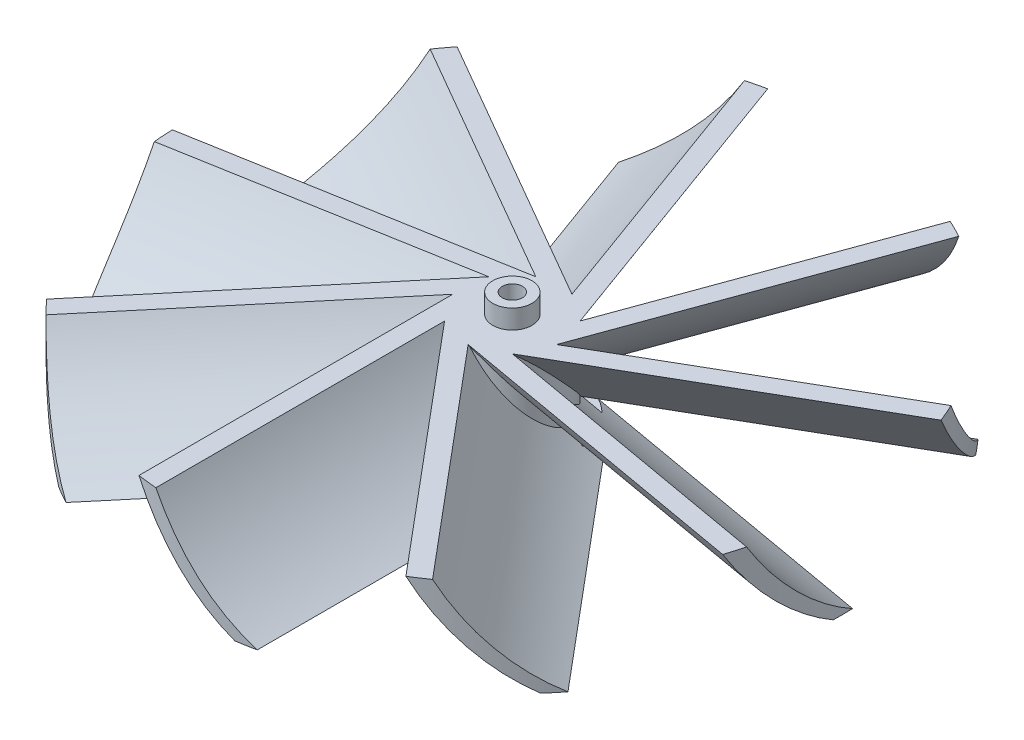
SolidWorks part; units mm, degrees
ref_plane "Front Plane" through (0, 0, 0) normal (0, 0, 1) x (1, 0, 0)
ref_plane "Top Plane" through (0, 0, 0) normal (0, 1, 0) x (1, 0, 0)
ref_plane "Right Plane" through (0, 0, 0) normal (1, 0, 0) x (0, 0, -1)
sketch "Sketch1" plane through (0, 0, 0) normal (0, 1, 0) x (1, 0, 0)
  circle A0 centre (0, 0) radius 5
  dimension "D1" = 10
extrude "Boss-Extrude1" add sketch "Sketch1" along normal blind 5 and the other way blind 5
sketch "Sketch2" plane through (0, 0, 0) normal (0, 0, 1) x (1, 0, 0)
  line L0 (5, 5) -> (-5, 5) construction
  line L1 (-5, 0.8212) -> (5.0825, -5) construction
  line L2 (-4.9175, 5) -> (0.856, -5) construction
  line L3 (-5, 5) -> (5, 5) construction
  line L4 (-5, -5) -> (-5, 5) construction
  line L5 (-5, -5) -> (5, -5) construction
  line L6 (5, 5) -> (5, -5) construction
  line L7 (-5, -5) -> (5, -5) construction
  line L8 (18.7428, 18.6603) -> (20.7428, 18.6603) construction
  line L9 (-4.9175, 5) -> (-2.9175, 5)
  line L10 (7.0825, -5) -> (5.0825, -5)
  line L11 (5, -5) -> (5, 5) construction
  line L12 (-5, 5) -> (-5, -5) construction
  line L13 (-4.9175, 5) -> (-4.9175, -5) construction
  line L15 (7.0825, 5) -> (7.0825, -5) construction
  arc A0 (-4.9175, 5) -> (5.0825, -5) centre (18.7428, 18.6603) ccw
  arc A1 (-2.9175, 5) -> (7.0825, -5) centre (20.7428, 18.6603) ccw
  dimension "D4" = 2
  dimension "D2" = 30
  dimension "D3" = 60
  dimension "D6" = 12
extrude "Boss-Extrude2" add sketch "Sketch2" along normal blind 45 contours A1 L10 A0 L9
sketch "Sketch3" plane through (0, 0, 0) normal (0, 0, 1) x (1, 0, 0)
  line L0 (0, 0) -> (0, 49.4452) construction
pattern_circular "CirPattern1" count 9 every 40 about axis through (0, 0, 0) along (0, 1, 0) of "Boss-Extrude2"
sketch "Sketch4" plane through (0, 5, 0) normal (0, 1, 0) x (1, 0, 0)
  circle A0 centre (0, 0) radius 34.5
  circle A1 centre (0, 0) radius 134.5
  dimension "D1" = 100
  dimension "D2" = 69
extrude "Cut-Extrude1" cut sketch "Sketch4" against normal blind 45
sketch "Sketch5" plane through (0, -5, 0) normal (0, -1, 0) x (1, 0, 0)
  line L1 (0, 0) -> (0, 7.5) construction
  line L2 (-0.6875, -1.0945) -> (-0.6875, 1.0945)
  circle A0 centre (0, 0) radius 7.5 construction
  arc A1 (-0.6875, -1.0945) -> (-0.6875, 1.0945) centre (0, 0) ccw
  point P8 (1.2925, 0)
  dimension "D1" = 15
  dimension "D3" = 2.585
  dimension "D4" = 1.98
extrude "Cut-Extrude2" cut sketch "Sketch5" against normal blind 5 contours A1 L2
sketch "Sketch6" plane through (0, -5, 0) normal (0, -1, 0) x (1, 0, 0)
  circle A0 centre (0, 0) radius 6.6348
  circle A1 centre (0, 0) radius 5
extrude "Boss-Extrude3" add sketch "Sketch6" against normal blind 1
sketch "Sketch7" plane through (0, 5, 0) normal (0, 1, 0) x (1, 0, 0)
  circle A0 centre (0, 0) radius 1.05
  circle A1 centre (0, 0) radius 2.05
  dimension "D1" = 2.1
  dimension "D2" = 4.1
extrude "Boss-Extrude4" add sketch "Sketch7" along normal blind 2
sketch "Sketch8" plane through (0, 5, 0) normal (0, 1, 0) x (1, 0, 0)
  circle A0 centre (0, 0) radius 1.05
extrude "Cut-Extrude3" cut sketch "Sketch8" against normal blind 2
